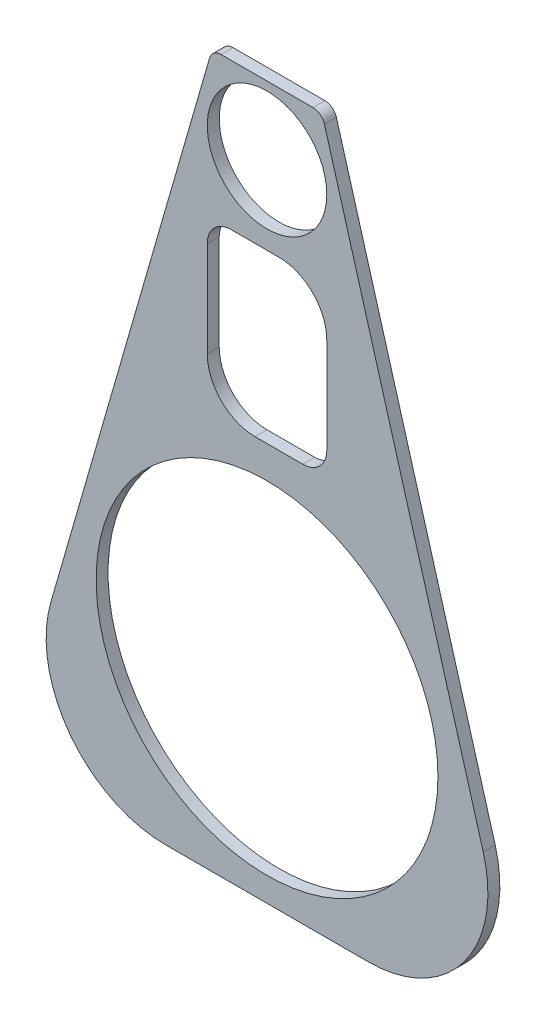
SolidWorks part; units mm, degrees
material "6061 Alloy"
ref_plane "Front" through (0, 0, 0) normal (0, 0, 1) x (1, 0, 0)
ref_plane "Top" through (0, 0, 0) normal (0, 1, 0) x (1, 0, 0)
ref_plane "Right" through (0, 0, 0) normal (1, 0, 0) x (0, 0, -1)
sketch "Sketch3" plane through (0, 0, 0) normal (0, 0, 1) x (1, 0, 0)
  line L1 (969.886, -1066.4574) -> (305.5143, 1238.3736)
  line L3 (-174.8832, 1238.3736) -> (-839.2549, -1066.4574)
  line L4 (65.3155, 1274.5248) -> (65.3155, -1694.2708) construction
  line L17 (-126.8393, 1274.5248) -> (257.4704, 1274.5248)
  line L19 (15.3155, -38.8919) -> (215.3155, -38.8919)
  line L20 (-184.6845, 161.1081) -> (-184.6845, 561.1081)
  line L21 (-84.6845, 661.1081) -> (115.3155, 661.1081)
  line L22 (315.3155, 61.1081) -> (315.3155, 461.1081)
  line L23 (-358.8163, -1704.9447) -> (489.4474, -1704.9447)
  line L24 (-184.6845, -38.8919) -> (315.3155, 661.1081) construction
  line L25 (-184.6845, 661.1081) -> (315.3155, -38.8919) construction
  arc A10 (-174.8832, 1238.3736) -> (-126.8393, 1274.5248) centre (-126.8393, 1224.5248) cw
  arc A11 (305.5143, 1238.3736) -> (257.4704, 1274.5248) centre (257.4704, 1224.5248) ccw
  circle A13 centre (65.3155, 988.5365) radius 250
  circle A14 centre (65.3155, -888.8919) radius 715
  arc A15 (-839.2549, -1066.4574) -> (-358.8163, -1704.9447) centre (-358.8163, -1204.9447) ccw
  arc A16 (489.4474, -1704.9447) -> (969.886, -1066.4574) centre (489.4474, -1204.9447) ccw
  arc A17 (-184.6845, 161.1081) -> (15.3155, -38.8919) centre (15.3155, 161.1081) ccw
  arc A18 (315.3155, 461.1081) -> (115.3155, 661.1081) centre (115.3155, 461.1081) ccw
  arc A19 (-184.6845, 561.1081) -> (-84.6845, 661.1081) centre (-84.6845, 561.1081) cw
  arc A20 (215.3155, -38.8919) -> (315.3155, 61.1081) centre (215.3155, 61.1081) ccw
  point P1 (65.3155, 311.1081)
  point P11 (60.2939, 331.5151)
  point P28 (-164.4625, 1274.5248)
  point P33 (295.0936, 1274.5248)
  point P40 (-1221.1605, -809.8312)
  point P41 (-906.9659, -748.7378)
  dimension "D4" = 500
  dimension "D5" = 700
  dimension "D6" = 500
  dimension "D7" = 500
  dimension "D8" = 500
  dimension "D9" = 50
  dimension "D11" = 50
  dimension "D2" = 1430
  dimension "D10" = 200
  dimension "D12" = 200
  dimension "D13" = 100
  dimension "D14" = 100
  dimension "D3" = 1200
  dimension "D15" = 820
  dimension "D16" = 820
  dimension "D17" = 300
  dimension "D18" = 300
extrude "Boss-Extrude1" add sketch "Sketch3" along normal blind 50 contours L3 L1 region at (860.9581, -1484.4931, 0)
